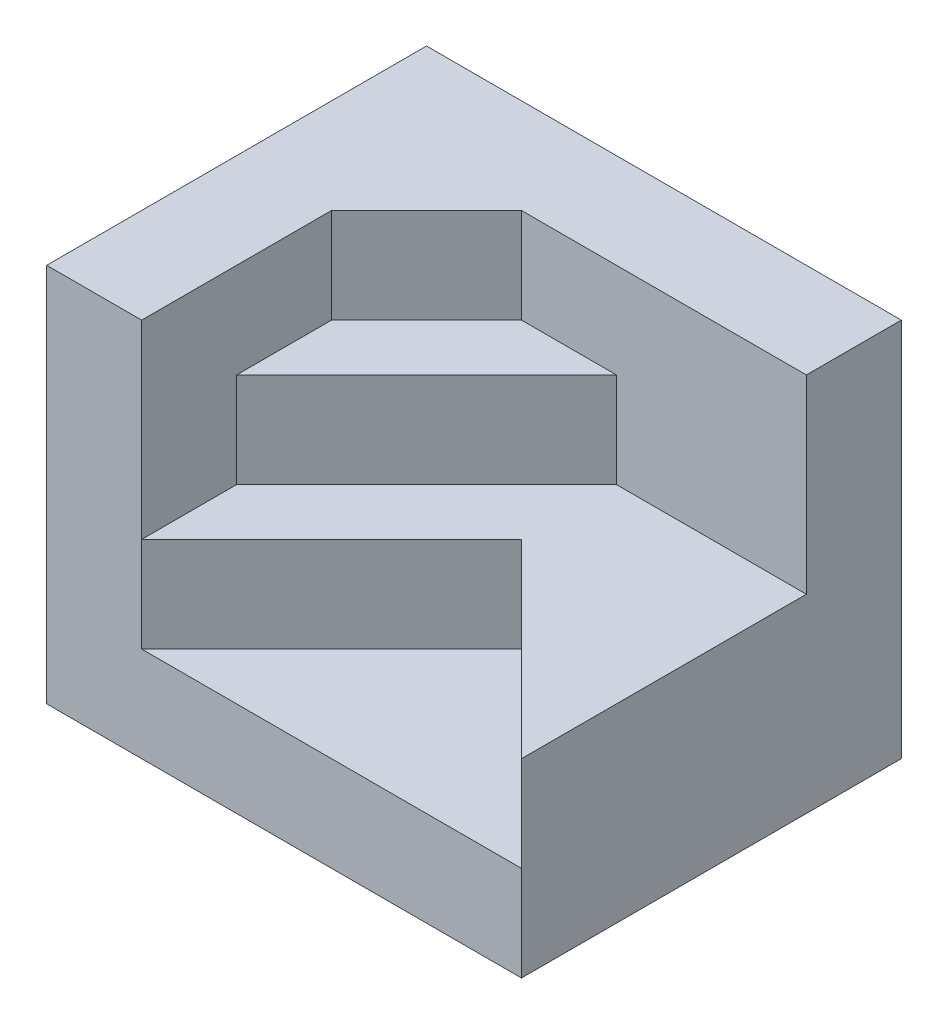
SolidWorks part; units mm, degrees
ref_plane "前基準面" through (0, 0, 0) normal (0, 0, 1) x (1, 0, 0)
ref_plane "上基準面" through (0, 0, 0) normal (0, 1, 0) x (1, 0, 0)
ref_plane "右基準面" through (0, 0, 0) normal (1, 0, 0) x (0, 0, -1)
sketch "草圖1" plane through (0, 0, 0) normal (0, 1, 0) x (1, 0, 0)
  line L0 (-7.5, -10) -> (-7.5, 5)
  line L1 (-12.5, -10) -> (12.5, -10)
  line L2 (-12.5, -10) -> (-12.5, 10)
  line L3 (-12.5, 10) -> (12.5, 10)
  line L4 (12.5, -10) -> (12.5, 10)
  line L5 (-12.5, -10) -> (12.5, 10) construction
  line L6 (-12.5, 10) -> (12.5, -10) construction
  line L7 (-7.5, 5) -> (12.5, 5)
  line L8 (-7.5, 0) -> (-2.5, 5)
  line L9 (-2.5, 5) -> (2.5, 5)
  line L10 (2.5, 5) -> (-7.5, -5)
  line L11 (-7.5, -5) -> (-7.5, -10)
  line L12 (-7.5, -10) -> (2.5, 0)
  line L13 (2.5, 0) -> (12.5, -10)
  point P0 (0, 0)
  dimension "D1" = 20
  dimension "D2" = 25
  dimension "D3" = 5
  dimension "D4" = 5
  dimension "D5" = 5
  dimension "D6" = 5
  dimension "D7" = 5
  dimension "D8" = 5
  dimension "D9" = 10
  dimension "D10" = 10
extrude "填料-伸長2" add sketch "草圖1" along normal blind 20 contours L0 L7 L4 L3 L2 L1 | L0 L8 L7 region at (-10, 0, 9.6798) region at (-5.8333, 0, -3.3333)
extrude "填料-伸長3" add sketch "草圖1<4>" along normal blind 15 contours L10 L7 L8 L0 region at (-3.6111, 0, -1.1111)
sketch "草圖1<4>" plane through (0, 0, 0) normal (0, 1, 0) x (1, 0, 0) same geometry as "草圖1"
extrude "填料-伸長4" add sketch "草圖1<5>" along normal blind 10 contours L12 L13 L4 L7 L10 L0 region at (4.7222, 0, 1.1111)
sketch "草圖1<5>" plane through (0, 0, 0) normal (0, 1, 0) x (1, 0, 0) same geometry as "草圖1"
extrude "填料-伸長5" add sketch "草圖1<6>" along normal blind 5 contours L13 L12 L1 region at (2.5, 0, 6.6667)
sketch "草圖1<6>" plane through (0, 0, 0) normal (0, 1, 0) x (1, 0, 0) same geometry as "草圖1"
